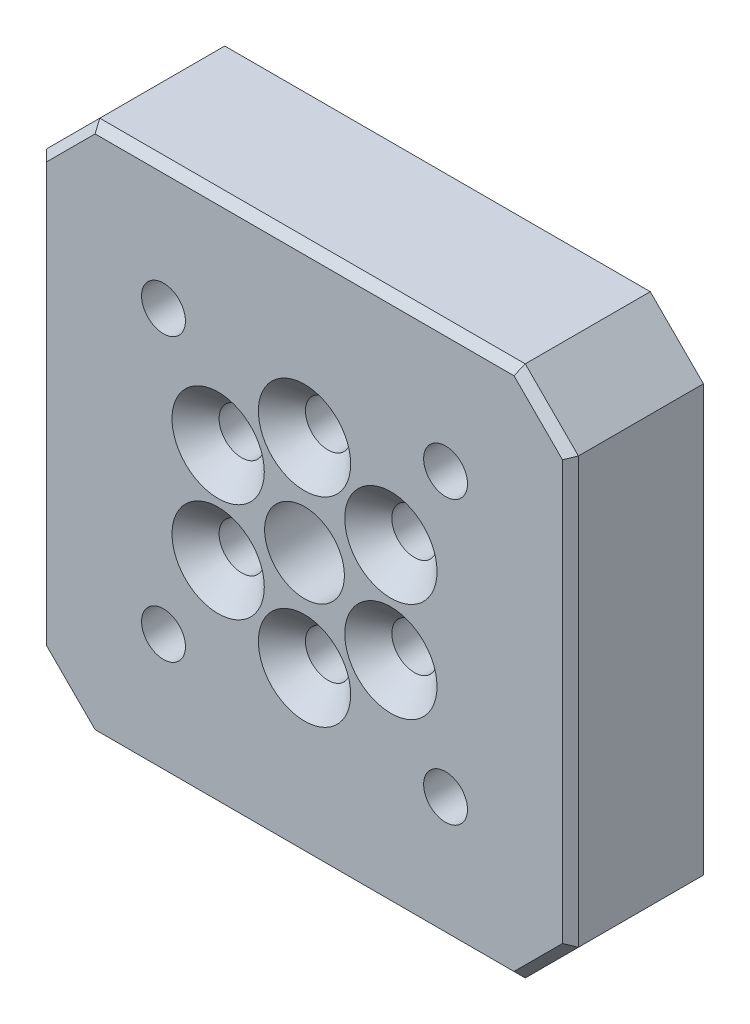
SolidWorks part; units mm, degrees
material "6061-T6 (SS)"
ref_plane "Front Plane" through (0, 0, 0) normal (0, 0, 1) x (1, 0, 0)
ref_plane "Top Plane" through (0, 0, 0) normal (0, 1, 0) x (1, 0, 0)
ref_plane "Right Plane" through (0, 0, 0) normal (1, 0, 0) x (0, 0, -1)
sketch "Sketch1" plane through (0, 0, 0) normal (0, 0, 1) x (1, 0, 0)
  line L1 (0, 0) -> (40, 0)
  line L2 (0, 0) -> (0, 40)
  line L3 (0, 40) -> (40, 40)
  line L4 (40, 0) -> (40, 40)
  dimension "D2" = 40
extrude "Boss-Extrude1" add sketch "Sketch1" along normal blind 10
sketch "Sketch18" plane through (0, 0, 10) normal (0, 0, 1) x (1, 0, 0)
  line L0 (40, 0) -> (40, 40) construction
  line L1 (0, 40) -> (0, 0) construction
  line L2 (0, 0) -> (40, 0) construction
  circle A0 centre (20, 20) radius 20
  point P1 (20, 20)
hole_wizard "Ø6.0mm Dowel Hole1" positions "Sketch18" profile "Sketch17" hole size "Ø6.0" standard "DIN" end condition through all
sketch "Sketch17" plane through (20, 20, 10) normal (1, 0, 0) x (0, -1, 0)
  line L0 (0, 0) -> (0, 10)
  line L1 (0, 10) -> (3, 10)
  line L2 (3, 10) -> (3, 0)
  line L5 (3, 0) -> (0, 0)
  line L11 (0, -6.35) -> (0, 107.95) construction
  dimension "Thru Hole Dia." = 6
  dimension "Thru Hole Depth" = 10
sketch "Sketch10" plane through (0, 0, 10) normal (0, 0, 1) x (1, 0, 0)
  point P5 (20, 27.5)
  point P12 (26.4952, 23.75)
  point P13 (26.4952, 16.25)
  point P14 (20, 12.5)
  point P15 (13.5048, 16.25)
  point P16 (13.5048, 23.75)
  dimension "D2" = 6
hole_wizard "CSK for M3 Hex Socket Countersunk Head Screw1" positions "Sketch10" profile "Sketch11" countersink size "M3" standard "DIN" end condition through all
sketch "Sketch11" plane through (20, 27.5, 10) normal (1, 0, 0) x (0, -1, 0)
  line L0 (0, 0) -> (0, 10)
  line L1 (0, 10) -> (1.7, 10)
  line L2 (1.7, 10) -> (1.7, 1.77)
  line L3 (1.7, 1.77) -> (3.47, 0)
  line L5 (3.47, 0) -> (0, 0)
  line L6 (-1.7, 1.77) -> (-3.47, 0) construction
  line L11 (0, -6.35) -> (0, 107.95) construction
  dimension "Thru Hole Dia." = 3.4
  dimension "Thru Hole Depth" = 10
  dimension "Near C'Sink Dia." = 6.94
  dimension "Near C'Sink Angle" = 90
sketch "Sketch12" plane through (0, 0, 10) normal (0, 0, 1) x (1, 0, 0)
  point P4 (9.3934, 30.6066)
  point P11 (30.6066, 30.6066)
  point P12 (30.6066, 9.3934)
  point P13 (9.3934, 9.3934)
  dimension "D2" = 4
hole_wizard "Tap Drill for M4 Tap1" positions "Sketch12" profile "Sketch13" hole size "M4" standard "DIN" end condition through all
sketch "Sketch13" plane through (9.3934, 30.6066, 10) normal (1, 0, 0) x (0, -1, 0)
  line L0 (0, 0) -> (0, 10)
  line L1 (0, 10) -> (1.65, 10)
  line L2 (1.65, 10) -> (1.65, 0)
  line L5 (1.65, 0) -> (0, 0)
  line L11 (0, -6.35) -> (0, 107.95) construction
  dimension "Thru Hole Dia." = 3.3
  dimension "Thru Hole Depth" = 10
chamfer "Chamfer1" distance 4 angle 45 4 edges at (40, 0, 5) (40, 40, 5) (0, 0, 5) (0, 40, 5)
chamfer "Chamfer2" distance 0.6 angle 45 8 edges at (40, 20, 10) (38, 38, 10) (38, 2, 10) (20, 0, 10) (2, 2, 10) (0, 20, 10) (2, 38, 10) (20, 40, 10)
